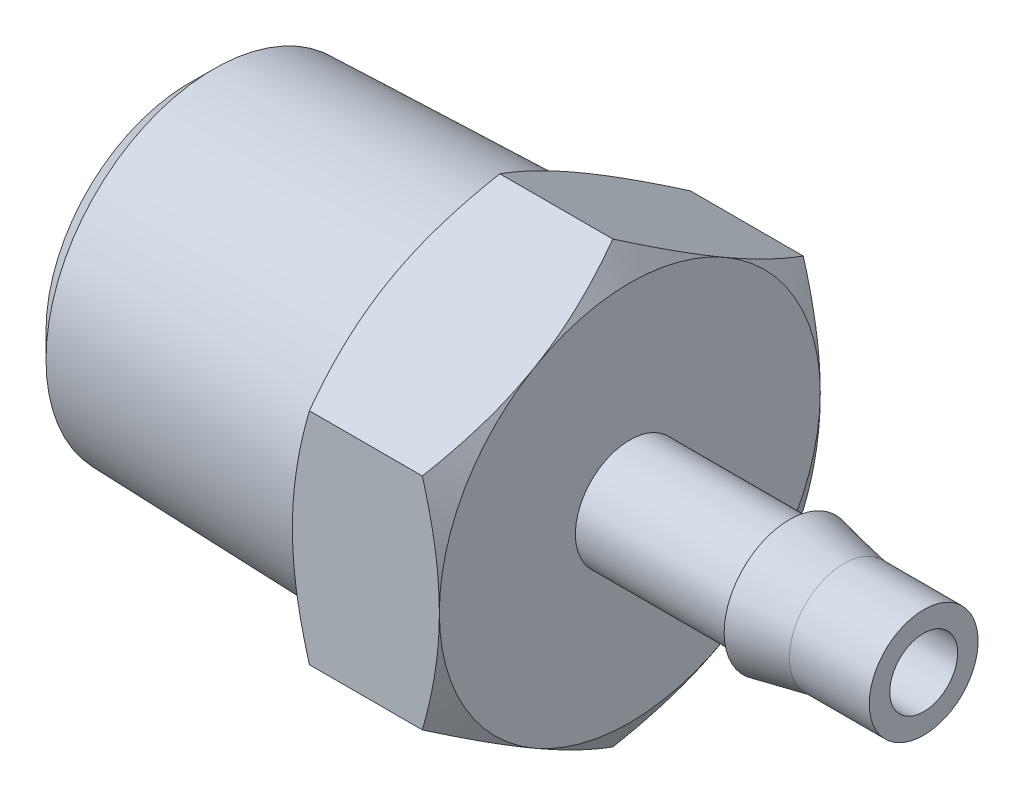
SolidWorks part; units mm, degrees
material "Alloy Steel (SS)"
ref_plane "Front Plane" through (0, 0, 0) normal (0, 0, 1) x (1, 0, 0)
ref_plane "Top Plane" through (0, 0, 0) normal (0, 1, 0) x (1, 0, 0)
ref_plane "Right Plane" through (0, 0, 0) normal (1, 0, 0) x (0, 0, -1)
sketch "Sketch1" plane through (0, 0, 0) normal (0, 0, 1) x (1, 0, 0)
  line L0 (-10.7156, 0) -> (10.7156, 0) construction
  line L1 (10.7156, 0) -> (10.7156, 5.6209) construction
  line L2 (-10.7156, 0) -> (-10.7156, 5.6209) construction
ref_plane "Plane1" through (-10.7156, 0, 0) normal (1, 0, 0) x (0, 0, -1)
sketch "Sketch8" plane through (-10.7156, 0, 0) normal (1, 0, 0) x (0, 0, -1)
  line L1 (0, 6.4158) -> (-5.5562, 3.2079)
  line L2 (-5.5562, 3.2079) -> (-5.5562, -3.2079)
  line L3 (-5.5562, -3.2079) -> (0, -6.4158)
  line L4 (0, -6.4158) -> (5.5563, -3.2079)
  line L5 (5.5563, -3.2079) -> (5.5563, 3.2079)
  line L6 (5.5563, 3.2079) -> (0, 6.4158)
  circle A0 centre (0, 0) radius 5.5562 construction
  dimension "Hex" = 11.1125
extrude "Hex ht" add sketch "Sketch8" against normal mid plane 4.2862 from vertex separate body starting at point (0, 0, 0)
sketch "Sketch2" plane through (-2.1431, 0, 0) normal (1, 0, 0) x (0, 0, -1)
  circle A0 centre (0, 0) radius 5.1435
  dimension "pipe od" = 10.287
extrude "L4" add sketch "Sketch2" against normal up to vertex (8.5725 mm away) draft 1.783 separate body up to point (-10.7156, 0, 0)
sketch "Sketch6" plane through (0, 0, 0) normal (0, 0, 1) x (1, 0, 0)
  line L0 (-9.9874, -4.8993) -> (-10.7156, -4.171)
  line L1 (-10.7156, -4.171) -> (-10.7156, -4.8766)
  line L2 (-10.7156, -4.8766) -> (-9.9874, -4.8993)
  line L7 (-10.7156, 4.8766) -> (-10.7156, -4.8766) construction
  line L8 (-10.7156, -4.8766) -> (-2.1431, -5.1435) construction
  dimension "D1" = 45
  dimension "D2" = 0.7056
sketch "Sketch4" plane through (-2.1431, 0, 0) normal (1, 0, 0) x (0, 0, -1)
  circle A1 centre (0, 0) radius 5.1435
  circle A2 centre (0, 0) radius 5.1435
  dimension "D1" = 0
curve "Helix/Spiral1" [suppressed] parameters "pitch"=0.9407, "angle 2"=1.783
sketch "Sketch5" plane through (0, 0, 0) normal (0, 0, 1) x (1, 0, 0)
  line L0 (-2.1431, 5.1435) -> (-1.7903, 4.5325)
  line L1 (-1.7903, 4.5325) -> (-1.6728, 4.5325)
  line L2 (-1.6728, 4.5325) -> (-1.2906, 5.1943)
  line L3 (-2.1431, 5.1435) -> (-1.32, 5.1435) construction
  line L6 (-1.7316, 5.1435) -> (-1.7316, 4.5325) construction
  line L7 (-1.9667, 4.838) -> (-1.4964, 4.838) construction
  line L9 (-2.1431, 5.1435) -> (-2.1725, 5.1943)
  line L10 (-2.1725, 5.1943) -> (-1.2906, 5.1943)
  dimension "thread angle" = 60
  dimension "D3" = 0.1176
  dimension "D4" = 0.4704
  dimension "D1" = 0.0508
sweep "Cut-Sweep3" [suppressed] cut profiles "Sketch5" path "Helix/Spiral1"
revolve "Cut-Revolve1" cut sketch "Sketch6" angle 360 about L0
combine bodies "Combine2" operation type add bodies to combine 136 107
sketch "Sketch9" plane through (0, 0, 0) normal (0, 0, 1) x (1, 0, 0)
  line L0 (-2.1431, 0.9906) -> (10.7156, 0.9906)
  line L1 (10.7156, 0.9906) -> (10.7156, 1.5875)
  line L2 (10.7156, 1.5875) -> (10.7156, -1.5875) construction
  line L5 (10.7156, 1.5875) -> (-2.1431, 1.5875)
  line L6 (-2.1431, 0.9906) -> (-2.1431, 1.5875)
  line L7 (-2.1431, 3.2079) -> (-2.1431, -3.2079) construction
  line L8 (10.7156, 0) -> (10.7156, 5.6209) construction
  line L9 (0, 0) -> (10.7156, 0) construction
  dimension "Dia" = 3.175
revolve "Revolve1" add sketch "Sketch9" angle 360 about L9
sketch "Sketch13" plane through (0, 0, 0) normal (0, 0, 1) x (1, 0, 0)
  line L0 (8.3873, 1.5875) -> (6.7998, 1.905)
  line L1 (6.7998, 1.905) -> (6.7998, 1.5875)
  line L2 (8.3873, 1.5875) -> (6.7998, 1.5875)
  line L3 (10.7156, 1.5875) -> (-2.1431, 1.5875) construction
  line L4 (6.7998, 1.5875) -> (4.4715, 1.5875) construction
  line L5 (10.7156, 1.5875) -> (2.1431, 1.5875) construction
  line L7 (4.4715, 1.5875) -> (2.1431, 1.5875) construction
  line L8 (6.7998, 1.905) -> (6.7998, -1.905) construction
  line L9 (10.7156, 1.5875) -> (8.3873, 1.5875) construction
  line L10 (2.1431, -3.2079) -> (2.1431, 3.2079) construction
  point P5 (6.7998, 0)
  dimension "Dia" = 3.81
  dimension "D2" = 1.5875
revolve "Revolve2" add sketch "Sketch13" angle 360 about L0
sketch "Sketch17" plane through (0, 0, 0) normal (0, 0, 1) x (1, 0, 0)
  line L0 (-2.1431, 1.905) -> (-1.5932, 1.5875)
  line L1 (-2.1431, 3.2079) -> (-2.1431, -3.2079) construction
  line L2 (6.7998, 1.5875) -> (2.1431, 1.5875) construction
  line L3 (-1.5932, 1.5875) -> (-2.1431, 1.5875)
  line L4 (-2.1431, 1.5875) -> (-2.1431, 1.905)
  dimension "D1" = 30
revolve "Revolve3" add sketch "Sketch17" angle 360 about L0
sketch "Sketch11" plane through (2.1431, 0, 0) normal (1, 0, 0) x (0, 0, -1)
  circle A0 centre (0, 0) radius 5.5562 construction
  circle A3 centre (0, 0) radius 5.5562
extrude "Cut-Extrude3" cut sketch "Sketch11" against normal through all draft 60 flip side to cut
sketch "Sketch12" plane through (-2.1431, 0, 0) normal (-1, 0, 0) x (0, 0, 1)
  circle A0 centre (0, 0) radius 5.5562 construction
  circle A1 centre (0, 0) radius 5.5562
extrude "Cut-Extrude5" cut sketch "Sketch12" against normal through all draft 60 flip side to cut
ref_plane "Plane2" through (0, 0, 0) normal (0, -0.7071, 0.7071) x (1, 0, 0)
sketch "Sketch14" plane through (-2.1431, 0, 0) normal (-1, 0, 0) x (0, 0, 1)
  circle A1 centre (0, 0) radius 0.9906
  circle A2 centre (0, 0) radius 0.9906 construction
extrude "Cut-Extrude6" cut sketch "Sketch14" against normal through all and the other way through all
sketch "Sketch19" plane through (-10.7156, 0, 0) normal (-1, 0, 0) x (0, 0, 1)
  circle A0 centre (0, 0) radius 3.6004
  dimension "D1" = 7.2009
extrude "Cut-Extrude7" cut sketch "Sketch19" against normal up to vertex (10.7156 mm away) up to point (0, 0, 0)
chamfer "Chamfer1" distance 0.2572 angle 45 1 edges at (-10.7156, 0, 3.6004)
sketch "Sketch18" plane through (0, 0, 0) normal (0, 0, 1) x (1, 0, 0)
  line L0 (-2.1431, -5.1435) -> (-10.7156, -4.8766)
  line L1 (-10.7156, -6.1119) -> (-10.7156, 6.1119) construction
  line L2 (-10.7156, 0) -> (10.7156, 0) construction
  line L3 (-10.7156, 4.8766) -> (-2.1431, 5.1435)
  point P9 (-6.4294, -5.01)
  dimension "D1" = 1.783
  dimension "D2" = 1.783
equation "\"D3@Sketch5\" = \"pitch@Helix/Spiral1\"*.125"
equation "\"D4@Sketch5\" = \"pitch@Helix/Spiral1\"*.50"
equation "\"D2@Sketch6\" = \"pitch@Helix/Spiral1\" * .75"
equation "\"A@Sketch9\" = \"Dia@Sketch9\" * 0.624"
equation "\"Dia@Sketch13\" = \"Dia@Sketch9\" * 1.2"
equation "\"D2@Sketch13\" = \"Dia@Sketch9\" * .5"
equation "\"Hx ht@Hex ht\" = \"Lg@Sketch1\" * .2"
equation "\"D3@Helix/Spiral1\" = \"Lg@Sketch1\" * .5"
equation "\"D1@Sketch18\" = \"angle 1@L4\""
equation "\"D2@Sketch18\" = \"D1@Sketch18\""
equation "\"D1@Sketch19\" = \"pipe od@Sketch2\" * .7"
equation "\"D1@Chamfer1\" = \"pipe od@Sketch2\" * .025"
